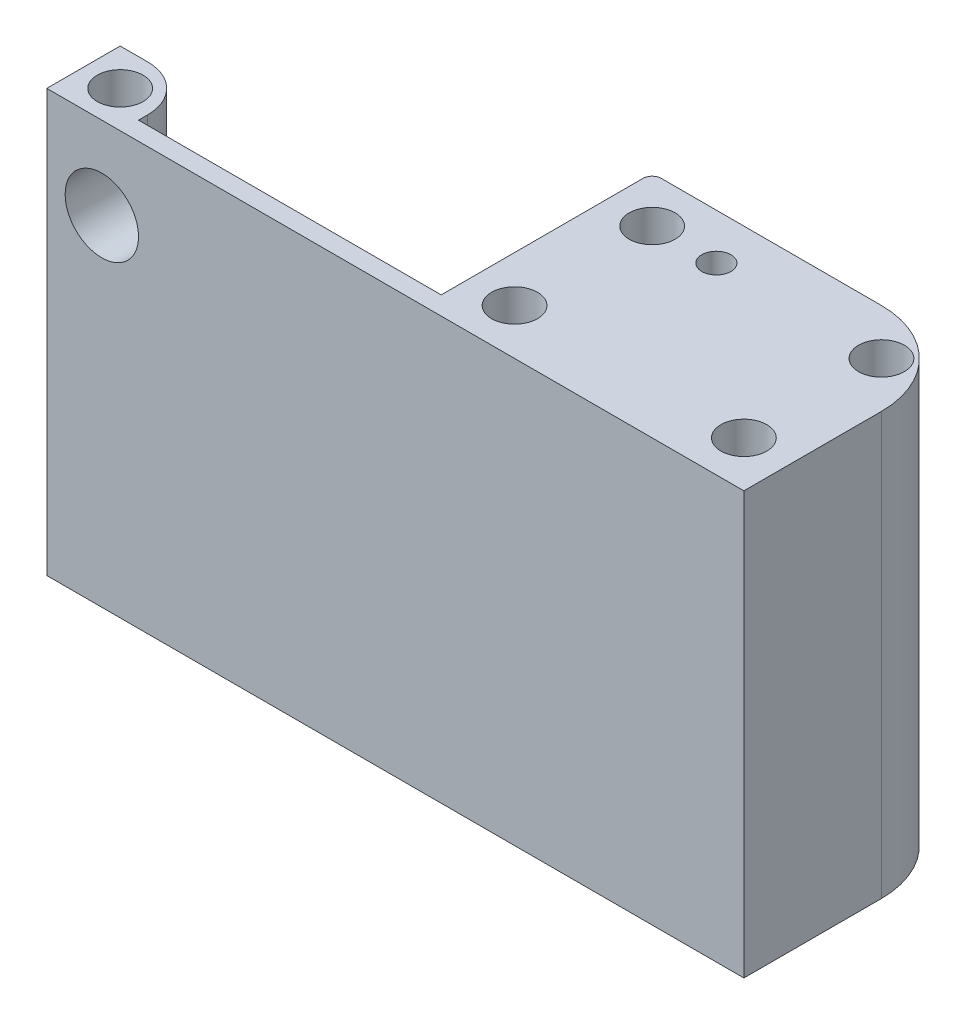
SolidWorks part; units mm, degrees
ref_plane "Front Plane" through (0, 0, 0) normal (0, 0, 1) x (1, 0, 0)
ref_plane "Top Plane" through (0, 0, 0) normal (0, 1, 0) x (1, 0, 0)
ref_plane "Right Plane" through (0, 0, 0) normal (1, 0, 0) x (0, 0, -1)
sketch "Sketch1" plane through (0, 0, 0) normal (0, 1, 0) x (1, 0, 0)
  line L0 (0, 8) -> (0, 0)
  line L1 (41, 2) -> (8, 2)
  line L2 (41, 2) -> (41, 25)
  line L3 (41, 25) -> (76, 25)
  line L4 (76, 25) -> (76, 0)
  line L5 (76, 0) -> (0, 0)
  line L6 (8, 2) -> (8, 8)
  line L7 (8, 8) -> (0, 8)
  dimension "D1" = 8
  dimension "D2" = 8
  dimension "D3" = 25
  dimension "D4" = 2
  dimension "D5" = 35
  dimension "D6" = 76
extrude "Boss-Extrude1" add sketch "Sketch1" along normal blind 46
fillet "Fillet5" radius 5 1 edges at (8, 23, -8)
hole_wizard "Ø5.0mm Dowel Hole1" positions "Sketch2" profile "Sketch3" hole size "Ø5.0" standard "ANSI Metric"
sketch "Sketch2" plane through (0, 46, 0) normal (0, 1, 0) x (1, 0, 0)
  line L0 (76, 0) -> (76, 25) construction
  line L1 (0, 0) -> (76, 0) construction
  line L2 (0, 0) -> (76, 0) construction
  line L3 (0, 8) -> (0, 0) construction
  point P4 (71, 5)
  point P18 (46, 5)
  point P19 (46, 20)
  point P20 (71, 20)
  point P21 (4, 4)
  dimension "D1" = 5
  dimension "D2" = 5
  dimension "D5" = 4
  dimension "D6" = 4
  dimension "D3" = 2
  dimension "D4" = 2
sketch "Sketch3" plane through (71, 46, -5) normal (1, 0, 0) x (0, 0, 1)
  line L0 (0, 0) -> (0, 8.5022)
  line L1 (0, 8.5022) -> (2.5, 7)
  line L2 (2.5, 7) -> (2.5, 0)
  line L5 (2.5, 0) -> (0, 0)
  line L10 (0, 8.5022) -> (-2.5, 7) construction
  line L11 (0, -6.35) -> (0, 107.95) construction
  dimension "Hole Dia." = 5
  dimension "Hole Depth" = 7
  dimension "Drill Angle" = 118
sketch "Sketch4" plane through (0, 46, 0) normal (0, 1, 0) x (1, 0, 0)
  line L0 (38, 0) -> (38, 37.5584) construction
  line L1 (0, 0) -> (76, 0) construction
  line L2 (76, 25) -> (41, 25) construction
  circle A0 centre (53, 20) radius 1.5875
  dimension "D3" = 3.175
  dimension "D1" = 15
  dimension "D2" = 5
extrude "Cut-Extrude1" cut sketch "Sketch4" against normal through all
sketch "Sketch6" plane through (0, 0, 0) normal (0, 1, 0) x (1, 0, 0)
  circle A1 centre (53, 20) radius 17.5
  dimension "D1" = 35
extrude "Cut-Extrude3" cut sketch "Sketch6" along normal blind 25 from offset 12
fillet "Fillet1" radius 10 1 edges at (76, 23, -25)
sketch "Sketch16" plane through (0, 0, 0) normal (0, 0, 1) x (1, 0, 0)
  circle A0 centre (6, 37) radius 4
  dimension "D1" = 8
  dimension "D2" = 37
  dimension "D3" = 6
extrude "Cut-Extrude5" cut sketch "Sketch16" against normal through all both and the other way through all
fillet "Fillet3" radius 1 2 edges at (41, 6, -25) (41, 41.5, -25)
fillet "Fillet4" radius 3 1 edges at (41, 24.5, -7.2623)
hole_wizard "Ø5.0mm Dowel Hole2" positions "Sketch17" profile "Sketch18" hole size "Ø5.0" standard "ANSI Metric"
sketch "Sketch17" plane through (0, 0, 0) normal (0, -1, 0) x (-1, 0, 0)
  line L1 (-76, 0) -> (-76, 15) construction
  line L2 (0, 0) -> (-76, 0) construction
  line L4 (0, 8) -> (0, 0) construction
  point P4 (-46, 5)
  point P18 (-71, 5)
  point P19 (-71, 20)
  point P20 (-46, 20)
  point P33 (-4, 4)
  point P35 (-4, 4)
  dimension "D1" = 5
  dimension "D2" = 5
  dimension "D5" = 4
  dimension "D6" = 4
  dimension "D3" = 2
  dimension "D4" = 2
sketch "Sketch18" plane through (46, 0, -5) normal (1, 0, 0) x (0, 0, -1)
  line L0 (0, 0) -> (0, 8.5022)
  line L1 (0, 8.5022) -> (2.5, 7)
  line L2 (2.5, 7) -> (2.5, 0)
  line L5 (2.5, 0) -> (0, 0)
  line L10 (0, 8.5022) -> (-2.5, 7) construction
  line L11 (0, -6.35) -> (0, 107.95) construction
  dimension "Hole Dia." = 5
  dimension "Hole Depth" = 7
  dimension "Drill Angle" = 118
